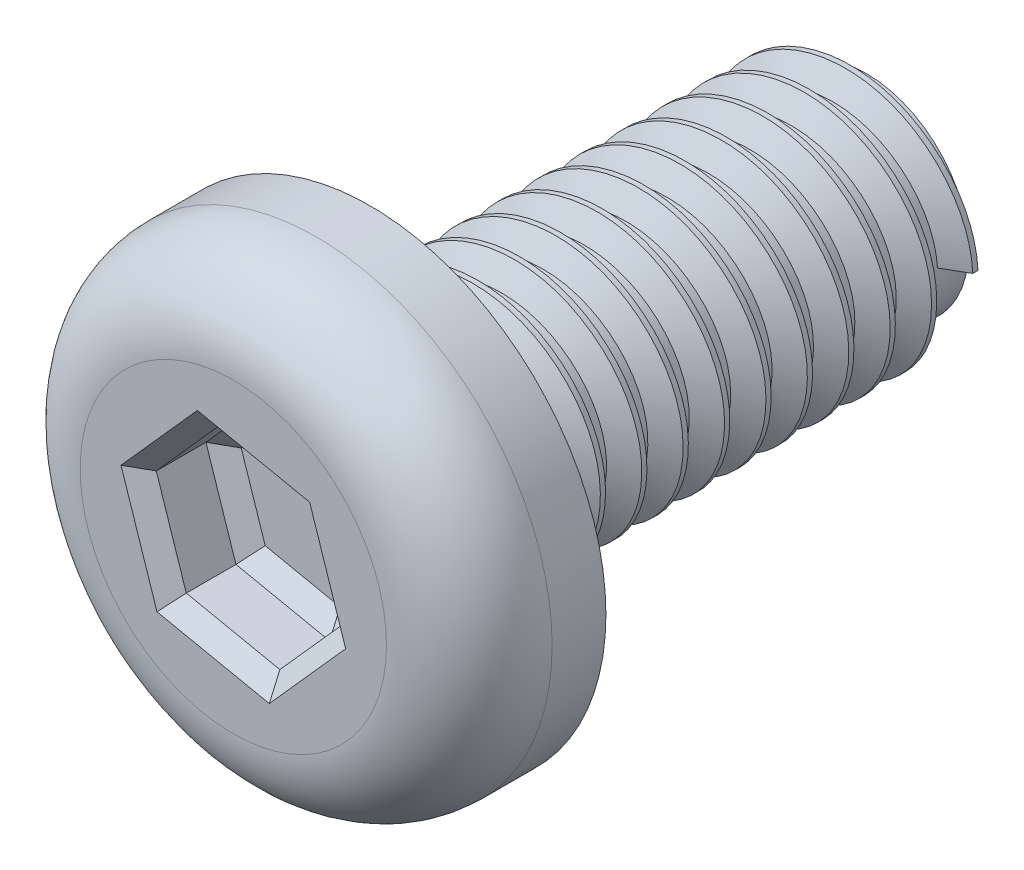
SolidWorks part; units mm, degrees
ref_plane "前视基准面" through (0, 0, 0) normal (0, 0, 1) x (1, 0, 0)
ref_plane "上视基准面" through (0, 0, 0) normal (0, 1, 0) x (1, 0, 0)
ref_plane "右视基准面" through (0, 0, 0) normal (1, 0, 0) x (0, 0, -1)
sketch "草图1" plane through (0, 0, 0) normal (0, 0, 1) x (1, 0, 0)
  circle A0 centre (0, 0) radius 2.85
  dimension "D1" = 5.7
extrude "凸台-拉伸1" add sketch "草图1" along normal blind 1.65
sketch "草图2" plane through (0, 0, 0) normal (0, 0, -1) x (-1, 0, 0)
  circle A0 centre (0, 0) radius 1.2295
  dimension "D1" = 2.459
extrude "凸台-拉伸2" add sketch "草图2" along normal blind 6
fillet "圆角1" radius 1 1 edges at (2.85, 0, 1.65)
sketch "草图3" plane through (0, 0, 1.65) normal (0, 0, 1) x (1, 0, 0)
  line L1 (0.3622, -1.0964) -> (1.1306, -0.2345)
  line L2 (1.1306, -0.2345) -> (0.7684, 0.8619)
  line L3 (0.7684, 0.8619) -> (-0.3622, 1.0964)
  line L4 (-0.3622, 1.0964) -> (-1.1306, 0.2345)
  line L5 (-1.1306, 0.2345) -> (-0.7684, -0.8619)
  line L6 (-0.7684, -0.8619) -> (0.3622, -1.0964)
  circle A0 centre (0, 0) radius 1 construction
  dimension "D1" = 2
extrude "切除-拉伸1" cut sketch "草图3" against normal blind 1
chamfer "倒角1" distance 0.2 angle 45 12 edges at (0.7464, -0.6655, 1.65) (0.9495, 0.3137, 1.65) (0.2031, 0.9792, 1.65) (-0.7464, 0.6655, 1.65) (-0.9495, -0.3137, 1.65) (-0.2031, -0.9792, 1.65) (-0.9495, -0.3137, 0.65) (-0.7464, 0.6655, 0.65) (0.2031, 0.9792, 0.65) (0.9495, 0.3137, 0.65) (0.7464, -0.6655, 0.65) (-0.2031, -0.9792, 0.65)
thread "螺纹线1" pitch 0.5 method extrude profile "螺纹线轮廓2" start angle 0, offset 0, length 0, pitch 0.5, diameter 2.459
ref_plane "基准面2" through (1.2295, 0, -6) normal (0, -1, 0) x (1, 0, 0)
sketch "螺纹线轮廓2" plane through (1.2295, 0, -6) normal (0, -1, 0) x (1, 0, 0)
  line L0 (0, 0) -> (0, 0.5) construction
  line L1 (0, 0) -> (0.2706, 0.1562)
  line L2 (0.2706, 0.1562) -> (0.2706, 0.2187)
  line L3 (0.2706, 0.2187) -> (0, 0.375)
  line L4 (0.2706, 0.1875) -> (0, 0.1875) construction
  line L11 (0, 0) -> (0, 0.375)
  point P2 (0, 0)
  dimension "Pitch" = 0.5
  dimension "Profile_Angle" = 60
  dimension "Profile_Land" = 0.0625
  dimension "Profile_Height" = 0.2706
